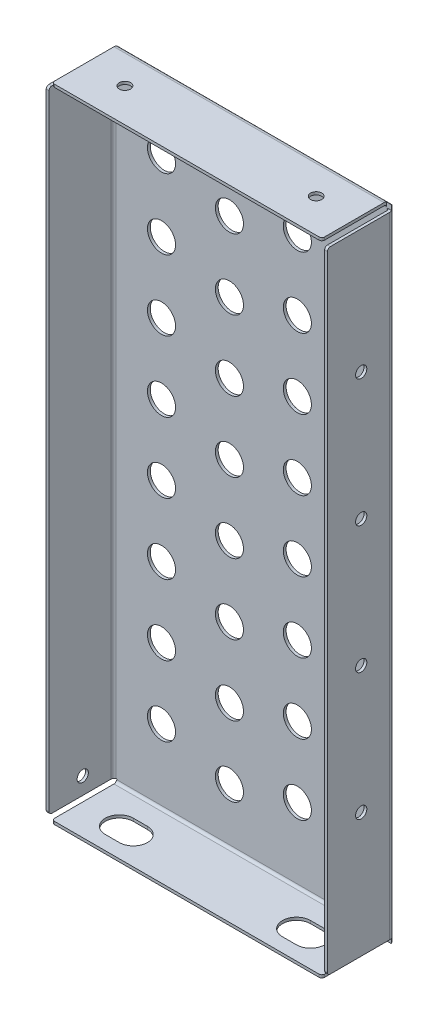
SolidWorks part; units mm, degrees
ref_plane "Спереди" through (0, 0, 0) normal (0, 0, 1) x (1, 0, 0)
ref_plane "Сверху" through (0, 0, 0) normal (0, 1, 0) x (1, 0, 0)
ref_plane "Справа" through (0, 0, 0) normal (1, 0, 0) x (0, 0, -1)
sketch "Эскиз1" plane through (0, 0, 0) normal (0, 0, 1) x (1, 0, 0)
  line L0 (0, 0) -> (0, 228)
  line L1 (0, 228) -> (100, 228)
  line L2 (100, 228) -> (100, 0)
  line L3 (100, 0) -> (0, 0)
  dimension "D1" = 228
  dimension "D2" = 100
extrude "Бобышка-Вытянуть1" add sketch "Эскиз1" along normal blind 1
sketch "Эскиз2" plane through (0, 0, 1) normal (0, 0, 1) x (1, 0, 0)
  line L2 (98, 227) -> (2, 227)
  line L4 (0, 0) -> (100, 0)
  line L5 (100, 0) -> (100, 228)
  line L6 (100, 228) -> (0, 228)
  line L7 (0, 228) -> (0, 0)
  line L8 (2, 0) -> (98, 0)
  line L9 (100, 2) -> (100, 226)
  line L10 (98, 228) -> (2, 228)
  line L11 (0, 226) -> (0, 2)
  line L12 (1, 227) -> (1, 1) construction
  line L13 (99, 227) -> (1, 227) construction
  line L14 (0, 228) -> (0, 0) construction
  line L15 (100, 228) -> (0, 228) construction
  line L16 (99, 1) -> (99, 227) construction
  line L17 (100, 0) -> (100, 228) construction
  line L18 (1, 1) -> (99, 1) construction
  line L19 (0, 0) -> (100, 0) construction
  line L20 (2, 1) -> (98, 1)
  line L22 (2, 0) -> (2, 1)
  line L23 (0, 2) -> (1, 2)
  line L24 (100, 0) -> (100, 228) construction
  line L25 (98, 1) -> (98, 0)
  line L26 (100, 2) -> (99, 2)
  line L27 (99, 2) -> (99, 226)
  line L28 (98, 228) -> (98, 227)
  line L29 (99, 226) -> (100, 226)
  line L30 (0, 226) -> (1, 226)
  line L31 (2, 227) -> (2, 228)
  line L32 (1, 226) -> (1, 2)
  line L33 (0, 0) -> (100, 0) construction
  dimension "D3" = 2
  dimension "D4" = 1
  dimension "D5" = 2
  dimension "D1" = 0
  dimension "D2" = 1
extrude "Бобышка-Вытянуть2" add sketch "Эскиз2" along normal blind 23
fillet "Скругление1" radius 0.9 4 edges at (50, 1, 1) (99, 114, 1) (1, 114, 1) (50, 227, 1)
fillet "Скругление2" radius 1.9 4 edges at (50, 228, 0) (100, 114, 0) (50, 0, 0) (0, 114, 0)
sketch "Эскиз3" plane through (0, 0, 1) normal (0, 0, 1) x (1, 0, 0)
  line L1 (0.2267, 226) -> (0.2267, 227.7733)
  line L2 (0.2267, 227.7733) -> (2, 227.7733)
  line L9 (0.2267, 226) -> (1.6709, 226)
  line L17 (118, 226.3291) -> (118, 227.7733)
  line L18 (119.7733, 226) -> (118.3291, 226)
  line L19 (119.7733, 227.7733) -> (118, 227.7733)
  line L20 (119.7733, 226) -> (119.7733, 227.7733)
  line L22 (2, 226.3291) -> (2, 227.7733)
  line L23 (2, 1.6709) -> (2, 0.2267)
  line L24 (119.7733, 2) -> (119.7733, 0.2267)
  line L25 (119.7733, 0.2267) -> (118, 0.2267)
  line L26 (119.7733, 2) -> (118.3291, 2)
  line L27 (118, 1.6709) -> (118, 0.2267)
  line L28 (0.2267, 2) -> (1.6709, 2)
  line L29 (0.2267, 0.2267) -> (2, 0.2267)
  line L30 (0.2267, 2) -> (0.2267, 0.2267)
  arc A4 (1.6709, 226) -> (2, 226.3291) centre (1.9, 226.1) ccw
  arc A5 (118.3291, 226) -> (118, 226.3291) centre (118.1, 226.1) cw
  arc A6 (118.3291, 2) -> (118, 1.6709) centre (118.1, 1.9) ccw
  arc A7 (1.6709, 2) -> (2, 1.6709) centre (1.9, 1.9) cw
extrude "Вырез-Вытянуть1" cut sketch "Эскиз3" against normal blind 22 and the other way blind 22
fillet "Скругление3" radius 1 8 edges at (98, 227.5, 24) (99.5, 226, 24) (0.5, 226, 24) (2, 227.5, 24) (0.5, 2, 24) (2, 0.5, 24) (98, 0.5, 24) (99.5, 2, 24)
sketch "Эскиз4" plane through (0, 0, 1) normal (0, 0, 1) x (1, 0, 0)
  line L0 (97, 1) -> (3, 1) construction
  line L1 (1, 3) -> (1, 225) construction
  circle A0 centre (18, 27) radius 5
  dimension "D1" = 10
  dimension "D2" = 26
  dimension "D3" = 17
extrude "Вырез-Вытянуть2" cut sketch "Эскиз4" against normal blind 10
sketch "Эскиз5" plane through (0, 0, 1) normal (0, 0, 1) x (1, 0, 0)
  circle A1 centre (18, 202) radius 5
  circle A2 centre (18, 177) radius 5
  circle A3 centre (18, 152) radius 5
  circle A4 centre (18, 127) radius 5
  circle A5 centre (18, 102) radius 5
  circle A6 centre (18, 77) radius 5
  circle A7 centre (18, 52) radius 5
  circle A8 centre (42.1481, 45.5295) radius 5
  circle A9 centre (42.1481, 20.5295) radius 5
  circle A10 centre (42.1481, 70.5295) radius 5
  circle A11 centre (42.1481, 95.5295) radius 5
  circle A12 centre (42.1481, 120.5295) radius 5
  circle A13 centre (42.1481, 145.5295) radius 5
  circle A14 centre (42.1481, 170.5295) radius 5
  circle A15 centre (42.1481, 195.5295) radius 5
  circle A16 centre (66.2963, 202) radius 5
  circle A17 centre (66.2963, 177) radius 5
  circle A18 centre (66.2963, 152) radius 5
  circle A19 centre (66.2963, 127) radius 5
  circle A20 centre (66.2963, 102) radius 5
  circle A21 centre (66.2963, 77) radius 5
  circle A22 centre (66.2963, 52) radius 5
  circle A23 centre (66.2963, 27) radius 5
extrude "Вырез-Вытянуть3" cut sketch "Эскиз5" against normal blind 10
sketch "Эскиз7" plane through (0, 228, 0) normal (0, 1, 0) x (1, 0, 0)
  circle A0 centre (16, -12) radius 2 construction
  circle A1 centre (84, -12) radius 2 construction
  circle A2 centre (16, -12) radius 2
  circle A3 centre (84, -12) radius 2
extrude "Вырез-Вытянуть4" cut sketch "Эскиз7" against normal blind 30
sketch "Эскиз8" plane through (0, 0, 0) normal (-1, 0, 0) x (0, 0, 1)
  circle A0 centre (12, 220) radius 2 construction
  circle A1 centre (12, 220) radius 2
extrude "Вырез-Вытянуть5" cut sketch "Эскиз8" against normal blind 30
sketch "Эскиз9" plane through (-1, 0, 0) normal (-1, 0, 0) x (0, 0, 1)
  circle A0 centre (12, 8) radius 2 construction
  circle A1 centre (12, 8) radius 2
extrude "Вырез-Вытянуть6" cut sketch "Эскиз9" against normal blind 30
sketch "Эскиз10" plane through (100, 0, 0) normal (1, 0, 0) x (0, 0, -1)
  circle A0 centre (-12, 46.3) radius 2 construction
  circle A1 centre (-12, 91.5) radius 2 construction
  circle A2 centre (-12, 136.7) radius 2 construction
  circle A3 centre (-12, 181.9) radius 2 construction
  circle A4 centre (-12, 46.3) radius 2
  circle A5 centre (-12, 91.5) radius 2
  circle A6 centre (-12, 136.7) radius 2
  circle A7 centre (-12, 181.9) radius 2
extrude "Вырез-Вытянуть7" cut sketch "Эскиз10" against normal blind 30
sketch "Эскиз11" plane through (0, 1, 0) normal (0, 1, 0) x (1, 0, 0)
  line L0 (16, -9) -> (21, -9)
  line L1 (16, -19) -> (21, -19)
  line L2 (50, -24) -> (50, -1.9) construction
  line L3 (84, -19) -> (79, -19)
  line L4 (84, -9) -> (79, -9)
  line L5 (1, -23) -> (1, -1.9) construction
  line L6 (0, -23) -> (0, -1.9) construction
  arc A0 (16, -9) -> (16, -19) centre (16, -14) ccw
  arc A1 (21, -19) -> (21, -9) centre (21, -14) ccw
  arc A2 (79, -19) -> (79, -9) centre (79, -14) cw
  arc A3 (84, -9) -> (84, -19) centre (84, -14) cw
  point P18 (0, -12.45)
  dimension "D1" = 5
  dimension "D3" = 15
  dimension "D2" = 5
  dimension "D4" = 50
extrude "Вырез-Вытянуть8" cut sketch "Эскиз11" against normal blind 10
